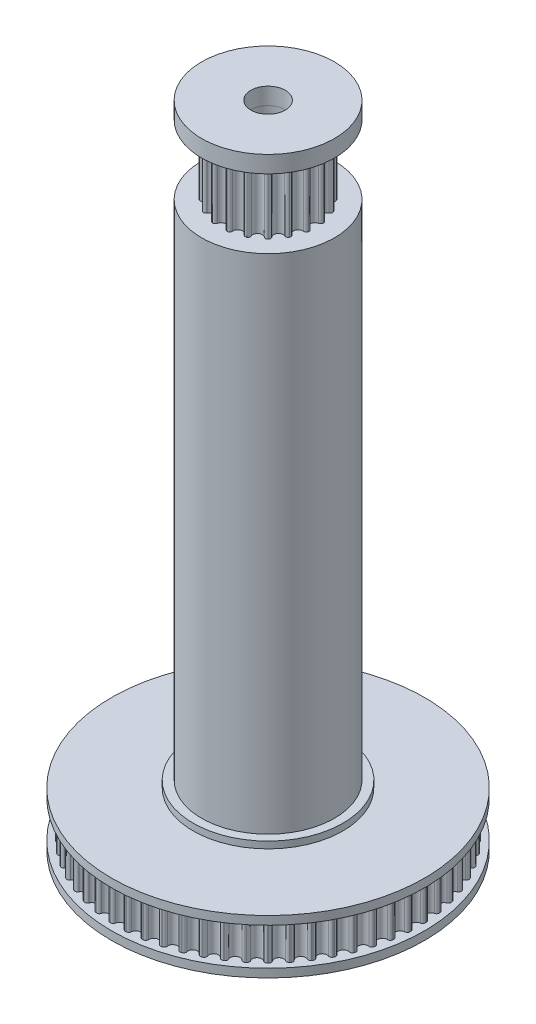
SolidWorks part; units mm, degrees
ref_plane "Front Plane" through (0, 0, 0) normal (0, 0, 1) x (1, 0, 0)
ref_plane "Top Plane" through (0, 0, 0) normal (0, 1, 0) x (1, 0, 0)
ref_plane "Right Plane" through (0, 0, 0) normal (1, 0, 0) x (0, 0, -1)
sketch "PulleyOffsets" plane through (0, 0, 0) normal (1, 0, 0) x (0, 0, -1)
  line L0 (53.721, 0) -> (-53.721, 0) construction
  line L1 (53.721, 107.442) -> (-53.721, 107.442) construction
  line L2 (0, 0) -> (0, 107.442) construction
  point P7 (0, 0)
  dimension "D1" = 107.442
ref_axis "Axis1" through (0, 34.9332, 0) along (0, -1, 0)
ref_plane "Big Pulley Plane" through (0, 0, 0) normal (0, 1, 0) x (1, 0, 0)
ref_plane "Small Pulley Plane" through (0, 107.442, 0) normal (0, 1, 0) x (1, 0, 0)
sketch "Sketch1" plane through (0, 0, 0) normal (0, 1, 0) x (1, 0, 0)
  line L0 (0, 0) -> (0, 28.2667) construction
  line L1 (0, 0) -> (2.9202, 27.7837) construction
  circle A0 centre (0, 0) radius 28.2667 construction
  circle A1 centre (0, 0) radius 27.0467 construction
  circle A2 centre (0, 27.9367) radius 0.89 construction
  circle A5 centre (2.9202, 27.7837) radius 0.89 construction
  arc A6 (0, 27.0467) -> (0.8804, 27.8061) centre (0, 27.9367) ccw
  arc A7 (0.8804, 27.8061) -> (1.3997, 28.2321) centre (1.3749, 27.7327) cw
  arc A8 (1.559, 28.2237) -> (2.031, 27.7458) centre (1.5314, 27.7245) cw
  arc A9 (2.8272, 26.8986) -> (2.031, 27.7458) centre (2.9202, 27.7837) cw
  arc A10 (1.3997, 28.2321) -> (1.559, 28.2237) centre (0, 0) cw
  arc A11 (0, 27.0467) -> (2.8272, 26.8986) centre (0, 0) ccw
  dimension "D1" = 56.5335
  dimension "D3" = 1.78
  dimension "D4" = 0.5
  dimension "D2" = 1.22
  dimension "D5" = 6
extrude "Boss-Extrude1" add sketch "Sketch1" along normal mid plane 7.112 contours A6 A11 A9 A8 A7 region at (0.001, 0, -0.0192)
pattern_circular "CirPattern1" count 60 over 360 about axis through (0, 34.9332, 0) along (0, -1, 0) of "Boss-Extrude1"
sketch "Sketch2" plane through (0, 0, 0) normal (1, 0, 0) x (0, 0, -1)
  line L10 (0, 3.5) -> (29.4415, 3.5) construction
  line L11 (0, 3.5) -> (0, 5.0875) construction
  line L12 (0, 5.0875) -> (29.4415, 5.0875) construction
  line L15 (29.4415, 3.5) -> (29.4415, 5.0875) construction
  line L20 (0, 34.9332) -> (0, -6.9932) construction
  line L22 (29.4415, 5.0875) -> (0, 5.0875)
  line L23 (29.4415, 5.0875) -> (29.4415, 3.5)
  line L24 (29.4415, 3.5) -> (0, 3.5)
  line L25 (0, 5.0875) -> (0, 3.5)
  dimension "D1" = 1.5875
  dimension "D2" = 29.4415
  dimension "D3" = 3.5
revolve "Revolve3" add sketch "Sketch2" angle 360 about axis through (0, 34.9332, 0) along (0, -1, 0) region at (0, 4.2937, -14.7207)
mirror "Mirror1" about plane through (0, 0, 0) normal (0, 1, 0) of "Revolve3"
sketch "Sketch3" plane through (0, 0, 0) normal (0, 1, 0) x (1, 0, 0)
  circle A0 centre (0, 0) radius 22.225
  dimension "D1" = 44.45
extrude "Cut-Extrude1" [suppressed] cut sketch "Sketch3" against normal through all both and the other way through all
sketch "Sketch6" plane through (0, 0, 0) normal (0, 1, 0) x (1, 0, 0)
  line L0 (0, 0) -> (0, 9.1676) construction
  line L1 (0, 0) -> (2.731, 8.405) construction
  circle A0 centre (0, 0) radius 9.1676 construction
  circle A1 centre (0, 0) radius 7.9476 construction
  circle A2 centre (0, 8.8376) radius 0.89 construction
  circle A5 centre (2.731, 8.405) radius 0.89 construction
  arc A6 (0, 7.9476) -> (0.8721, 8.6598) centre (0, 8.8376) ccw
  arc A7 (0.8721, 8.6598) -> (1.4405, 9.0537) centre (1.362, 8.5599) cw
  arc A8 (1.4277, 9.0557) -> (1.8466, 8.5054) centre (1.3498, 8.5618) cw
  arc A9 (2.4559, 7.5586) -> (1.8466, 8.5054) centre (2.731, 8.405) cw
  arc A10 (1.4405, 9.0537) -> (1.4277, 9.0557) centre (0, 0) cw construction
  arc A11 (0, 7.9476) -> (2.4559, 7.5586) centre (0, 0) ccw
  arc A12 (1.4405, 9.0537) -> (1.4277, 9.0557) centre (0, 0) cw
  dimension "D3" = 1.78
  dimension "D4" = 0.5
  dimension "D2" = 1.22
  dimension "D1" = 18.3352
  dimension "D5" = 18
extrude "Boss-Extrude2" add sketch "Sketch6" along normal mid plane 13 from surface contours A6 A11 A9 A8 A7 region at (0.0089, 0, -0.0564) starting at plane "Small Pulley Plane"
pattern_circular "CirPattern2" count 20 over 360 about axis through (0, 34.9332, 0) along (0, -1, 0) of "Boss-Extrude2"
sketch "Sketch4" plane through (0, 0, 0) normal (0, 0, 1) x (1, 0, 0)
  line L0 (14.0875, 5.0875) -> (-14.0875, 5.0875) construction
  line L1 (29.4415, 5.0875) -> (-29.4415, 5.0875) construction
  line L2 (-14.0875, 5.0875) -> (-14.0875, 6.3575)
  line L3 (-14.0875, 6.3575) -> (-12.5, 6.3575)
  line L4 (-12.5, 6.3575) -> (-12.5, 100.942)
  line L5 (0, 0) -> (0, 117.117) construction
  line L6 (12.5, 6.3575) -> (12.5, 100.942) construction
  line L7 (14.0875, 6.3575) -> (12.5, 6.3575) construction
  line L8 (14.0875, 5.0875) -> (14.0875, 6.3575) construction
  line L9 (-12.5, 100.942) -> (12.5, 100.942) construction
  line L10 (-14.0875, 5.0875) -> (0, 5.0875)
  line L11 (0, 5.0875) -> (0, 100.942)
  line L12 (0, 100.942) -> (-12.5, 100.942)
  line L13 (1.841, 100.942) -> (3.5054, 100.942) construction
  line L14 (0.8721, 113.942) -> (-0.8721, 113.942) construction
  line L15 (-12.5, 117.117) -> (0, 117.117)
  line L16 (-12.5, 117.117) -> (-12.5, 113.942)
  line L17 (-12.5, 113.942) -> (0, 113.942)
  line L18 (0, 117.117) -> (0, 113.942)
  line L19 (-12.5, 100.942) -> (-12.5, 113.942) construction
  point P14 (0, 5.0875)
  dimension "D1" = 1.27
  dimension "D2" = 1.5875
  dimension "D3" = 25
  dimension "D4" = 3.175
revolve "Revolve4" add sketch "Sketch4" angle 360 about L11
sketch "Sketch7" plane through (0, 117.117, 0) normal (0, 1, 0) x (1, 0, 0)
  circle A0 centre (0, 0) radius 3.2385
  dimension "D1" = 6.477
extrude "Cut-Extrude2" cut sketch "Sketch7" against normal through all both and the other way through all
equation "\"TEETH_NUM\"= 60"
equation "\"TOOTH_PITCH\"= 3mm"
equation "\"PITCH_LINE_OFFSET\"= .015in"
equation "\"DIAMETER_PER_GROOVE\"= \"OUTSIDE_DIAMETER\" / \"TEETH_NUM\" * 1in"
equation "\"PITCH_DIAMETER\"= ( ( \"TEETH_NUM\" * 3 - 1.31 ) / 3.1415 + .415 ) * 1mm"
equation "\"OUTSIDE_DIAMETER\"= \"PITCH_DIAMETER\" - \"PITCH_LINE_OFFSET\" * 2"
equation "\"D1@Sketch1\"=\"OUTSIDE_DIAMETER\""
equation "\"TOOTH_HEIGHT\"= 1.22mm"
equation "\"D2@Sketch1\"=\"TOOTH_HEIGHT\""
equation "\"TOOTH_DIAMETER\"= 1.78mm"
equation "\"INTERNAL_RADIUS\"= .5mm"
equation "\"D3@Sketch1\"=\"TOOTH_DIAMETER\""
equation "\"D5@Sketch1\"=360 / \"TEETH_NUM\""
equation "\"D4@Sketch1\"=\"INTERNAL_RADIUS\""
equation "\"D1@CirPattern1\"=\"TEETH_NUM\""
equation "\"BELT_GAP\"= 7mm"
equation "\"D2@Sketch2\"=\"PITCH_DIAMETER\"/2+1/32"
equation "\"D3@Sketch2\"=\"BELT_GAP\"/2"
equation "\"2_TEETH_NUM\"= 20"
equation "\"2_PITCH_DIAMETER\"= ( ( \"2_TEETH_NUM\" * 3 - 1.31 ) / 3.1415 + .415 ) * 1mm"
equation "\"2_OUTSIDE_DIAMETER\"= \"2_PITCH_DIAMETER\" - \"PITCH_LINE_OFFSET\" * 2"
equation "\"2_DIAMETER_PER_GROOVE\"= \"2_OUTSIDE_DIAMETER\" / \"2_TEETH_NUM\" * 1in"
equation "\"D5@Sketch6\"=360/\"2_TEETH_NUM\""
equation "\"D1@Sketch6\"=\"2_OUTSIDE_DIAMETER\""
equation "\"D2@Sketch6\"=\"TOOTH_HEIGHT\""
equation "\"D3@Sketch6\"=\"TOOTH_DIAMETER\""
equation "\"D4@Sketch6\"=\"INTERNAL_RADIUS\""
equation "\"2_BELT_GAP\"= 13mm"
equation "\"D1@CirPattern2\"=\"2_TEETH_NUM\""
equation "\"D1@Boss-Extrude2\"=\"2_BELT_GAP\""
equation "\"Pulley_OffSets\"= 4.23"
equation "\"D1@PulleyOffsets\" = \"Pulley_OffSets\""
